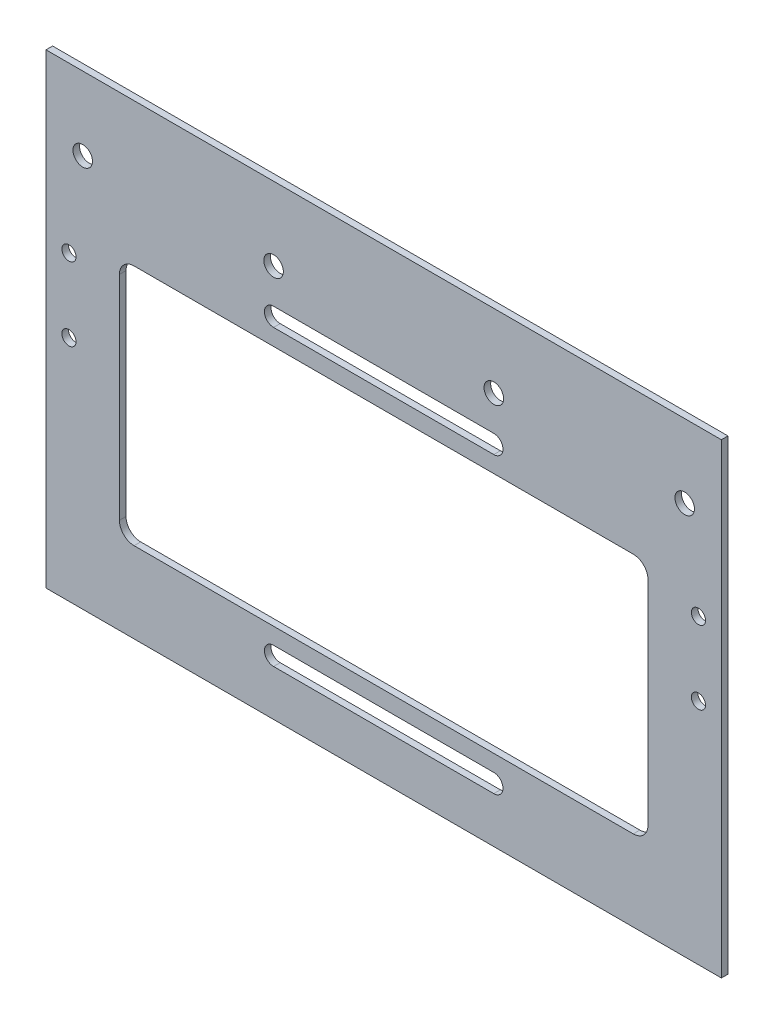
SolidWorks part; units mm, degrees
ref_plane "Front Plane" through (0, 0, 0) normal (0, 0, 1) x (1, 0, 0)
ref_plane "Top Plane" through (0, 0, 0) normal (0, 1, 0) x (1, 0, 0)
ref_plane "Right Plane" through (0, 0, 0) normal (1, 0, 0) x (0, 0, -1)
sketch "Sketch1" plane through (0, 0, 0) normal (0, 0, 1) x (1, 0, 0)
  line L1 (-116.84, 80.645) -> (116.84, 80.645)
  line L2 (-116.84, 80.645) -> (-116.84, -80.645)
  line L3 (-116.84, -80.645) -> (116.84, -80.645)
  line L4 (116.84, 80.645) -> (116.84, -80.645)
  line L5 (-116.84, 80.645) -> (116.84, -80.645) construction
  line L6 (-116.84, -80.645) -> (116.84, 80.645) construction
  line L7 (-86.36, 31.115) -> (86.36, 31.115)
  line L8 (-91.44, 26.035) -> (-91.44, -47.625)
  line L9 (-86.36, -52.705) -> (86.36, -52.705)
  line L10 (91.44, 26.035) -> (91.44, -47.625)
  line L11 (-91.44, 31.115) -> (91.44, -52.705) construction
  line L12 (-91.44, -52.705) -> (91.44, 31.115) construction
  arc A0 (86.36, -52.705) -> (91.44, -47.625) centre (86.36, -47.625) ccw
  arc A1 (86.36, 31.115) -> (91.44, 26.035) centre (86.36, 26.035) cw
  arc A2 (-91.44, 26.035) -> (-86.36, 31.115) centre (-86.36, 26.035) cw
  arc A3 (-86.36, -52.705) -> (-91.44, -47.625) centre (-86.36, -47.625) cw
  point P0 (0, 0)
  point P5 (0, -10.795)
  dimension "D7" = 5.08
  dimension "D1" = 25.4
  dimension "D2" = 161.29
  dimension "D3" = 182.88
  dimension "D4" = 83.82
  dimension "D5" = 27.94
  dimension "D6" = 233.68
extrude "Boss-Extrude1" add sketch "Sketch1" along normal blind 2.286
sketch "Sketch2" plane through (0, 0, 2.286) normal (0, 0, 1) x (1, 0, 0)
  line L0 (38.1, 40.005) -> (-38.1, 40.005) construction
  line L1 (38.1, 36.83) -> (-38.1, 36.83)
  line L2 (38.1, 43.18) -> (-38.1, 43.18)
  line L3 (-91.44, 26.035) -> (-91.44, -47.625) construction
  line L4 (-91.44, -10.795) -> (91.44, -10.795) construction
  line L5 (-91.44, 26.035) -> (-91.44, -47.625) construction
  line L6 (91.44, -47.625) -> (91.44, 26.035) construction
  line L7 (38.1, -61.595) -> (-38.1, -61.595) construction
  line L8 (38.1, -58.42) -> (-38.1, -58.42)
  line L9 (38.1, -64.77) -> (-38.1, -64.77)
  arc A0 (38.1, 36.83) -> (38.1, 43.18) centre (38.1, 40.005) ccw
  arc A1 (-38.1, 43.18) -> (-38.1, 36.83) centre (-38.1, 40.005) ccw
  arc A2 (38.1, -58.42) -> (38.1, -64.77) centre (38.1, -61.595) cw
  arc A3 (-38.1, -64.77) -> (-38.1, -58.42) centre (-38.1, -61.595) cw
  point P2 (0, 40.005)
  point P7 (-91.44, -10.795)
  point P19 (0, -61.595)
  dimension "D1" = 76.2
  dimension "D2" = 50.8
  dimension "D3" = 6.35
extrude "Cut-Extrude1" cut sketch "Sketch2" against normal through all
hole_wizard "1/4 Clearance Hole1" positions "Sketch4" profile "Sketch3" hole size "1/4" standard "ANSI Inch" end condition through all
sketch "Sketch4" plane through (0, 0, 2.286) normal (0, 0, 1) x (1, 0, 0)
  line L2 (116.84, 80.645) -> (-116.84, 80.645) construction
  line L3 (-38.1, 55.245) -> (38.1, 55.245) construction
  point P0 (-38.1, 55.245)
  point P8 (38.1, 55.245)
  point P22 (0, 55.245)
  dimension "D1" = 76.2
  dimension "D3" = 25.4
sketch "Sketch3" plane through (-38.1, 55.245, 2.286) normal (1, 0, 0) x (0, -1, 0)
  line L0 (0, 0) -> (0, 2.286)
  line L1 (0, 2.286) -> (3.3782, 2.286)
  line L2 (3.3782, 2.286) -> (3.3782, 0)
  line L5 (3.3782, 0) -> (0, 0)
  line L11 (0, -6.35) -> (0, 107.95) construction
  dimension "Thru Hole Dia." = 6.7564
  dimension "Thru Hole Depth" = 2.286
hole_wizard "1/4 Clearance Hole2" positions "Sketch8" profile "Sketch7" hole size "1/4" standard "ANSI Inch" end condition through all
sketch "Sketch8" plane through (0, 0, 2.286) normal (0, 0, 1) x (1, 0, 0)
  line L0 (-116.84, 80.645) -> (-116.84, -80.645) construction
  line L1 (116.84, -80.645) -> (116.84, 80.645) construction
  line L2 (116.84, 80.645) -> (-116.84, 80.645) construction
  point P0 (-104.14, 55.245)
  point P2 (104.14, 55.245)
  dimension "D1" = 12.7
  dimension "D2" = 12.7
  dimension "D3" = 25.4
sketch "Sketch7" plane through (-104.14, 55.245, 2.286) normal (1, 0, 0) x (0, -1, 0)
  line L0 (0, 0) -> (0, 2.286)
  line L1 (0, 2.286) -> (3.3782, 2.286)
  line L2 (3.3782, 2.286) -> (3.3782, 0)
  line L5 (3.3782, 0) -> (0, 0)
  line L11 (0, -6.35) -> (0, 107.95) construction
  dimension "Thru Hole Dia." = 6.7564
  dimension "Thru Hole Depth" = 2.286
hole_wizard "#10 (0.1935) Diameter Hole1" positions "Sketch10" profile "Sketch9" hole size "#10" standard "ANSI Inch" end condition through all
sketch "Sketch10" plane through (0, 0, 2.286) normal (0, 0, 1) x (1, 0, 0)
  line L2 (-116.84, 80.645) -> (-116.84, -80.645) construction
  line L3 (-108.9025, -1.651) -> (-108.9025, 23.749) construction
  line L6 (-115.2525, 30.099) -> (-102.5525, 30.099) construction
  line L7 (-115.2525, 30.099) -> (-115.2525, -8.001) construction
  line L9 (-102.5525, 30.099) -> (-102.5525, -8.001) construction
  line L10 (-115.2525, 30.099) -> (-102.5525, -8.001) construction
  line L11 (-115.2525, -8.001) -> (-102.5525, 30.099) construction
  point P0 (-108.9025, 23.749)
  point P2 (-108.9025, -1.651)
  dimension "D1" = 25.4
  dimension "D3" = 7.9375
  dimension "D4" = 38.1
  dimension "D5" = 12.7
sketch "Sketch9" plane through (-108.9025, 23.749, 2.286) normal (1, 0, 0) x (0, -1, 0)
  line L0 (0, 0) -> (0, 2.286)
  line L1 (0, 2.286) -> (2.4574, 2.286)
  line L2 (2.4574, 2.286) -> (2.4574, 0)
  line L5 (2.4574, 0) -> (0, 0)
  line L11 (0, -6.35) -> (0, 107.95) construction
  dimension "Thru Hole Dia." = 4.9149
  dimension "Thru Hole Depth" = 2.286
mirror "Mirror1" about plane through (0, 0, 0) normal (1, 0, 0) of "#10 (0.1935) Diameter Hole1"
